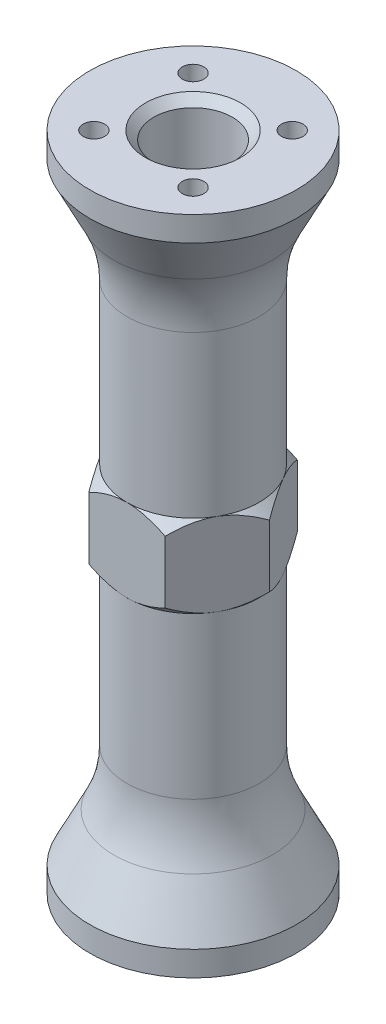
SolidWorks part; units mm, degrees
ref_plane "Front Plane" through (0, 0, 0) normal (0, 0, 1) x (1, 0, 0)
ref_plane "Top Plane" through (0, 0, 0) normal (0, 1, 0) x (1, 0, 0)
ref_plane "Right Plane" through (0, 0, 0) normal (1, 0, 0) x (0, 0, -1)
sketch "Sketch1" plane through (0, 0, 0) normal (0, 0, 1) x (1, 0, 0)
  line L0 (0, -40) -> (0, 40)
  line L1 (0, 40) -> (-12.5, 40)
  line L2 (-12.5, 40) -> (-12.5, 37)
  line L3 (-12.5, 37) -> (-8, 28)
  line L4 (-8, 28) -> (-8, -28)
  line L5 (-8, 0) -> (0, 0) construction
  line L6 (-12.5, -37) -> (-8, -28)
  line L7 (-12.5, -40) -> (-12.5, -37)
  line L8 (0, -40) -> (-12.5, -40)
  dimension "D1" = 12.5
  dimension "D2" = 3
  dimension "D3" = 8
  dimension "D4" = 80
  dimension "D5" = 12
revolve "Revolve1" add sketch "Sketch1" angle 360 about L0
sketch "Sketch2" plane through (0, 40, 0) normal (0, 1, 0) x (1, 0, 0)
  line L1 (6, -6) -> (-6, -6) construction
  line L2 (6, -6) -> (6, 6) construction
  line L3 (6, 6) -> (-6, 6) construction
  line L4 (-6, -6) -> (-6, 6) construction
  line L5 (6, -6) -> (-6, 6) construction
  line L6 (6, 6) -> (-6, -6) construction
  circle A0 centre (-6, 6) radius 1.3
  circle A1 centre (6, 6) radius 1.3
  circle A2 centre (-6, -6) radius 1.3
  circle A3 centre (6, -6) radius 1.3
  point P0 (0, 0)
  dimension "D1" = 12
  dimension "D2" = 2.6
extrude "Cut-Extrude1" cut sketch "Sketch2" against normal blind 7
mirror "Mirror1" about plane through (0, 0, 0) normal (0, 1, 0) of "Cut-Extrude1"
sketch "Sketch3" plane through (0, 0, 0) normal (1, 0, 0) x (0, 0, -1)
  line L0 (-5, 31.7) -> (0, 36.7)
  line L1 (8, 28) -> (-8, 28) construction
  line L2 (0, 36.7) -> (0, -36.7)
  line L3 (0, 0) -> (-5, 0) construction
  line L4 (-5, -31.7) -> (-5, 31.7)
  line L5 (-8, 28) -> (-8, -28) construction
  line L6 (-5, -31.7) -> (0, -36.7)
  line L7 (-4.7, 33) -> (-4.7, 32) construction
  line L8 (-4.7, 33) -> (-7.3, 33) construction
  dimension "D1" = 3
  dimension "D2" = 45
  dimension "D3" = 1
revolve "Cut-Revolve1" cut sketch "Sketch3" angle 360 about L2
sketch "Sketch4" plane through (0, 40, 0) normal (0, 1, 0) x (1, 0, 0)
  circle A3 centre (0, 0) radius 4.75
  dimension "D1" = 9.5
extrude "Cut-Extrude2" cut sketch "Sketch4" against normal through all
fillet "Fillet1" radius 15 2 edges at (0, 28, -8) (0, -28, -8)
fillet "Fillet2" radius 4 2 edges at (0, -31.7, 5) (0, 31.7, 5)
ref_plane "Plane1" through (0, 0, 0) normal (0, 1, 0) x (1, 0, 0)
sketch "Sketch5" plane through (0, 0, 0) normal (0, 1, 0) x (1, 0, 0)
  line L1 (4.6188, 8) -> (-4.6188, 8)
  line L2 (-4.6188, 8) -> (-9.2376, 0)
  line L3 (-9.2376, 0) -> (-4.6188, -8)
  line L4 (-4.6188, -8) -> (4.6188, -8)
  line L5 (4.6188, -8) -> (9.2376, 0)
  line L6 (9.2376, 0) -> (4.6188, 8)
  circle A0 centre (0, 0) radius 8 construction
  circle A1 centre (0, 0) radius 8 construction
  circle A2 centre (0, 0) radius 7
extrude "Boss-Extrude1" add sketch "Sketch5" along normal mid plane 10
sketch "Sketch6" plane through (0, 0, 0) normal (0, 0, 1) x (1, 0, 0)
  line L0 (-8, 5) -> (-9.2376, 3.7624)
  line L1 (-9.2376, 5) -> (-9.2376, -5) construction
  line L2 (-9.2376, 3.7624) -> (-9.2376, 5)
  line L3 (-9.2376, 5) -> (-8, 5)
  dimension "D1" = 45
revolve "Cut-Revolve2" cut sketch "Sketch6" angle 360 about axis through (0, -40, 0) along (0, -1, 0)
mirror "Mirror2" about plane through (0, 0, 0) normal (0, 1, 0) of "Cut-Revolve2"
chamfer "Chamfer1" distance 1 angle 45 2 edges at (0, 40, 4.75) (0, -40, 4.75)
